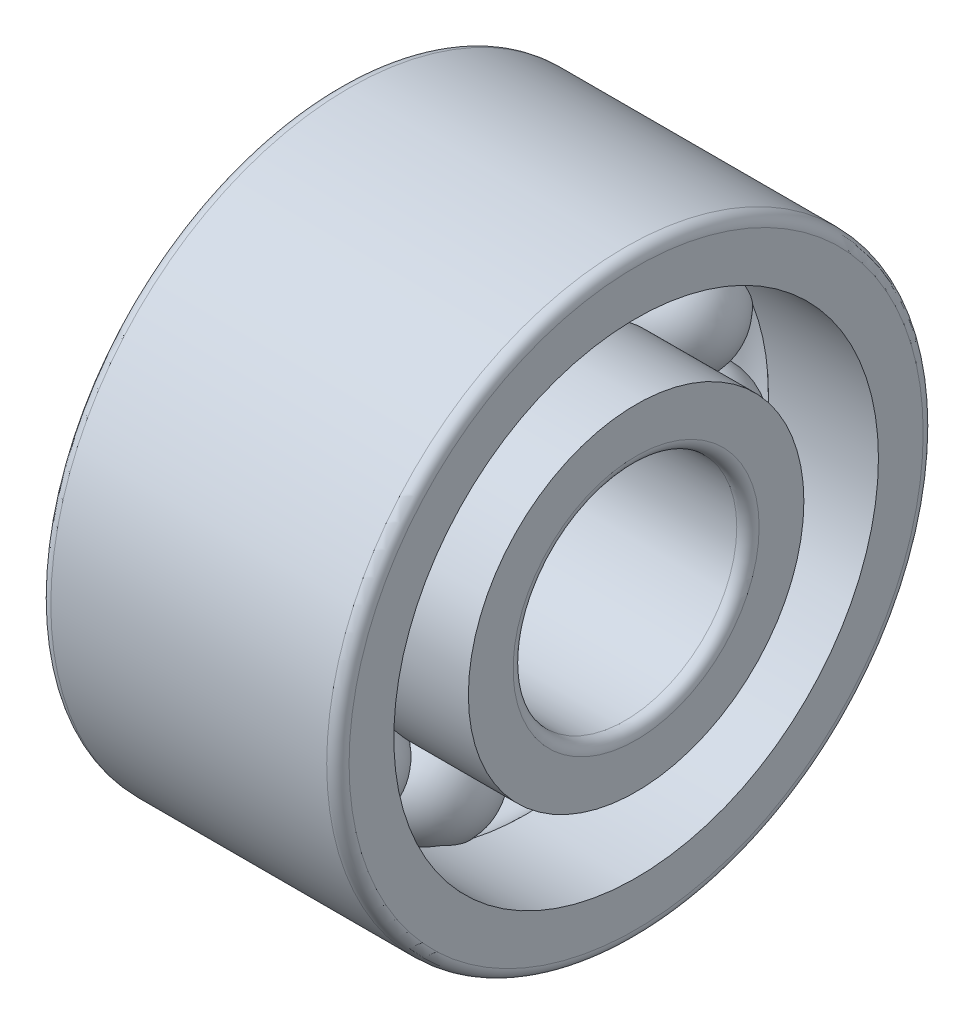
SolidWorks part; units mm, degrees
ref_plane "Plane1" through (0, 0, 0) normal (0, 0, 1) x (1, 0, 0)
ref_plane "Plane2" through (0, 0, 0) normal (0, 1, 0) x (1, 0, 0)
ref_plane "Plane3" through (0, 0, 0) normal (1, 0, 0) x (0, 0, -1)
sketch "Clipboard" plane through (0, 0, 0) normal (0, 0, 1) x (1, 0, 0)
  line L0 (-10, 0) -> (10, 0) construction
  line L1 (0, 0) -> (21.9499, -4.2666)
  line L2 (0, 0) -> (2.7496, -0.048)
  line L3 (0, 0) -> (22.3573, 0.3902)
  line L4 (0, 0) -> (-22.3573, -0.3902)
  dimension "BallCLRad" = 2.75
  dimension "Count" = 359
  dimension "Show_count" = 359
  dimension "Max_count" = 11
  dimension "Min_count" = 1
sketch "CagSpiSke" plane through (0, 0, 0) normal (0, 0, 1) x (1, 0, 0)
  line L0 (0.075, 2.625) -> (0.075, 2.875)
  line L1 (0.075, 2.875) -> (-0.075, 2.875)
  line L2 (-0.075, 2.875) -> (-0.075, 2.625)
  line L3 (-0.075, 2.625) -> (0.075, 2.625)
  line L4 (-20.6375, 0) -> (20.6375, 0) construction
  line L5 (0, 0) -> (0, 23.7692) construction
  dimension "Thickness" = 0.15
  dimension "OD" = 5.75
  dimension "ID" = 5.25
revolve "CageSpine" add sketch "CagSpiSke" angle 0.001 about L4 reverse direction yes
ref_axis "Axis1" through (-50, 0, 0) along (1, 0, 0)
sketch "CagBalSke" plane through (0, 0, 0) normal (0, 0, 1) x (1, 0, 0)
  line L0 (-0.825, 2.75) -> (0.825, 2.75)
  line L1 (-1.905, 2.75) -> (1.905, 2.75) construction
  line L2 (-10, 0) -> (10, 0) construction
  line L3 (0, 0) -> (0, 24) construction
  arc A0 (0.825, 2.75) -> (-0.825, 2.75) centre (0, 2.75) cw
  dimension "CageWallOD" = 1.65
  dimension "BallCLRad" = 2.75
revolve "CageBall" [suppressed] add sketch "CagBalSke" angle 360 about L1 reverse direction yes
pattern_circular "CageBalls" [suppressed] count 11 every 32.727 about axis through (-50, 0, 0) along (1, 0, 0)
sketch "CagTrmODSke" plane through (0, 0, 0) normal (0, 0, 1) x (1, 0, 0)
  line L0 (0.826, 2.875) -> (0.826, 3.576)
  line L1 (0.826, 3.576) -> (-0.826, 3.576)
  line L2 (-0.826, 3.576) -> (-0.826, 2.875)
  line L3 (-0.826, 2.875) -> (0.826, 2.875)
  line L4 (-20.6375, 0) -> (20.6375, 0) construction
  line L5 (0, 0) -> (0, 25) construction
  dimension "Width" = 1.652
  dimension "ID" = 5.75
  dimension "OD" = 7.152
revolve "CageTrimOD" [suppressed] cut sketch "CagTrmODSke" angle 360 about L4 reverse direction yes
sketch "CagTrmIDSke" plane through (0, 0, 0) normal (0, 0, 1) x (1, 0, 0)
  line L0 (0.826, 1.926) -> (0.826, 2.625)
  line L1 (0.826, 2.625) -> (-0.826, 2.625)
  line L2 (-0.826, 2.625) -> (-0.826, 1.926)
  line L3 (-0.826, 1.926) -> (0.826, 1.926)
  line L4 (-20.6375, 0) -> (20.6375, 0) construction
  line L5 (0, 0) -> (0, 25) construction
  dimension "ID" = 3.852
  dimension "OD" = 5.25
  dimension "Width" = 1.652
revolve "CageTrimID" [suppressed] cut sketch "CagTrmIDSke" angle 360 about L4 reverse direction yes
sketch "BalSimSke" plane through (0, 0, 0) normal (0, 0, 1) x (1, 0, 0)
  line L0 (-10, 0) -> (10, 0) construction
  line L1 (-10, 2.75) -> (10, 2.75) construction
  line L2 (0, 0) -> (0, 23) construction
  circle A0 centre (0, 2.75) radius 0.75
  dimension "Ball_diameter" = 1.5
  dimension "BallCLRad" = 2.75
revolve "BallsSimplified" [suppressed] add sketch "BalSimSke" angle 360 about L0
sketch "BalDetSke" plane through (0, 0, 0) normal (0, 0, 1) x (1, 0, 0)
  line L0 (-0.75, 2.75) -> (0.75, 2.75)
  line L1 (-1.905, 2.75) -> (1.905, 2.75) construction
  line L2 (0, 0) -> (0, 25) construction
  arc A0 (0.75, 2.75) -> (-0.75, 2.75) centre (0, 2.75) cw
  dimension "Ball_diameter" = 1.5
  dimension "BallCLRad" = 2.75
revolve "BallDetailed" add sketch "BalDetSke" angle 360 about L1 reverse direction yes
sketch "InnRacSke" plane through (0, 0, 0) normal (0, 0, 1) x (1, 0, 0)
  line L0 (-0.525, 2.25) -> (-2, 2.25)
  line L1 (-2, 2.25) -> (-2, 1.65)
  line L2 (-1.85, 1.5) -> (1.85, 1.5)
  line L3 (2, 1.65) -> (2, 2.25)
  line L4 (2, 2.25) -> (0.525, 2.25)
  line L5 (-20.6375, 0) -> (20.6375, 0) construction
  line L6 (0, 0) -> (0, 30) construction
  arc A0 (-2, 1.65) -> (-1.85, 1.5) centre (-1.85, 1.65) ccw
  arc A1 (1.85, 1.5) -> (2, 1.65) centre (1.85, 1.65) ccw
  arc A2 (0.525, 2.25) -> (-0.525, 2.25) centre (0, 2.75) cw
  dimension "Fillet_radius" = 0.15
  dimension "Ball_diameter" = 1.45
  dimension "ID" = 3
  dimension "OD" = 4.5
  dimension "Width" = 4
  dimension "BallCLRad" = 2.75
revolve "InnerRace" add sketch "InnRacSke" angle 360 about L5 reverse direction yes
sketch "OutRacSke" plane through (0, 0, 0) normal (0, 0, 1) x (1, 0, 0)
  line L0 (-0.525, 3.25) -> (-2, 3.25)
  line L1 (-2, 3.25) -> (-2, 3.85)
  line L2 (-1.85, 4) -> (1.85, 4)
  line L3 (2, 3.85) -> (2, 3.25)
  line L4 (2, 3.25) -> (0.525, 3.25)
  line L5 (-20.6375, 0) -> (20.6375, 0) construction
  line L6 (0, 0) -> (0, 30) construction
  arc A0 (-2, 3.85) -> (-1.85, 4) centre (-1.85, 3.85) cw
  arc A1 (1.85, 4) -> (2, 3.85) centre (1.85, 3.85) cw
  arc A2 (0.525, 3.25) -> (-0.525, 3.25) centre (0, 2.75) ccw
  dimension "Fillet_radius" = 0.15
  dimension "Ball_diameter" = 1.45
  dimension "OD" = 8
  dimension "ID" = 6.5
  dimension "Width" = 4
  dimension "BallCLRad" = 2.75
revolve "OuterRace" add sketch "OutRacSke" angle 360 about L5 reverse direction yes
pattern_circular "BallsDetailed" count 11 every 32.727 about axis through (-50, 0, 0) along (1, 0, 0) of "BallDetailed"
equation "\"BallCLRad@Clipboard\" = ( \"OD@OutRacSke\" + \"ID@InnRacSke\" ) / 4"
equation "\"BallCLRad@BalSimSke\" = \"BallCLRad@Clipboard\""
equation "\"BallCLRad@BalDetSke\" = \"BallCLRad@Clipboard\""
equation "\"BallCLRad@InnRacSke\" = \"BallCLRad@Clipboard\""
equation "\"BallCLRad@OutRacSke\" = \"BallCLRad@Clipboard\""
equation "\"Ball_diameter@InnRacSke\" = \"Ball_diameter@BalDetSke\" - 0.05"
equation "\"Ball_diameter@OutRacSke\" = \"Ball_diameter@BalDetSke\" - 0.05"
equation "\"Ball_diameter@BalSimSke\" = \"Ball_diameter@BalDetSke\""
equation "\"Width@OutRacSke\" = \"Width@InnRacSke\""
equation "\"Fillet_radius@OutRacSke\" = \"Fillet_radius@InnRacSke\""
equation "\"Max_count@Clipboard\" = int( 3.14159265 / atn(( \"Ball_diameter@BalDetSke\" / 2) / sqr( \"BallCLRad@Clipboard\"  *  \"BallCLRad@Clipboard\" - ( \"Ball_diameter@BalDetSke\" / 2) *  ( \"Ball_diameter@BalDetSke\" / 2))))"
equation "\"Max_count@Clipboard\" = ((sgn( \"Max_count@Clipboard\" - \"Count@Clipboard\" )-1)*( \"Max_count@Clipboard\" - \"Count@Clipboard\" ))/-2+ \"Count@Clipboard\""
equation "\"Count@BallsDetailed\" = int( \"Show_count@Clipboard\" ) "
equation "\"Count@BallsDetailed\" = ((sgn( \"Count@BallsDetailed\" - \"Max_count@Clipboard\" )-1)*( \"Count@BallsDetailed\" - \"Max_count@Clipboard\" ))/-2+ \"Max_count@Clipboard\""
equation "\"Count@BallsDetailed\" = ((sgn( \"Count@BallsDetailed\" - \"Min_count@Clipboard\" )+1)*( \"Count@BallsDetailed\" - \"Min_count@Clipboard\"))/2 +\"Min_count@Clipboard\""
equation "\"Angle@BallsDetailed\" = 360.0 / \"Max_count@Clipboard\""
equation "\"BallCLRad@CagBalSke\" = \"BallCLRad@Clipboard\""
equation "\"Count@CageBalls\" = \"Count@BallsDetailed\""
equation "\"Angle@CageBalls\" = \"Angle@BallsDetailed\""
equation "\"Angle@CageSpine\" =  \"Angle@CageBalls\" * ( \"Count@CageBalls\" -1 + int( \"Count@CageBalls\" / \"Max_count@Clipboard\" ) )  + 0.001 -  int( \"Count@CageBalls\" / \"Max_count@Clipboard\" ) * 0.001"
equation "\"Angle@CageSpine\" =  \"Angle@CageSpine\" * int( \"Min_count@Clipboard\" / 2) + int(1 / \"Min_count@Clipboard\")  * 0.001"
equation "\"CageWallOD@CagBalSke\" =  \"Ball_diameter@BalDetSke\" * 1.1"
equation "\"Thickness@CagSpiSke\" =  \"Ball_diameter@BalDetSke\" * 0.1"
equation "\"OD@CagTrmODSke\" = \"BallCLRad@Clipboard\" * 2 + \"CageWallOD@CagBalSke\" + 0.002"
equation "\"ID@CagTrmODSke\" = \"BallCLRad@Clipboard\" * 2 + \"Ball_diameter@BalDetSke\" / 6"
equation "\"OD@CagTrmIDSke\" = \"BallCLRad@Clipboard\" * 2 - \"Ball_diameter@BalDetSke\" / 6"
equation "\"ID@CagTrmIDSke\" = \"BallCLRad@Clipboard\" * 2 - \"CageWallOD@CagBalSke\" + 0.002"
equation "\"OD@CagSpiSke\" = \"ID@CagTrmODSke\""
equation "\"ID@CagSpiSke\" = \"OD@CagTrmIDSke\""
equation "\"Width@CagTrmODSke\" = \"CageWallOD@CagBalSke\" + 0.002"
equation "\"Width@CagTrmIDSke\" = \"CageWallOD@CagBalSke\" + 0.002"
